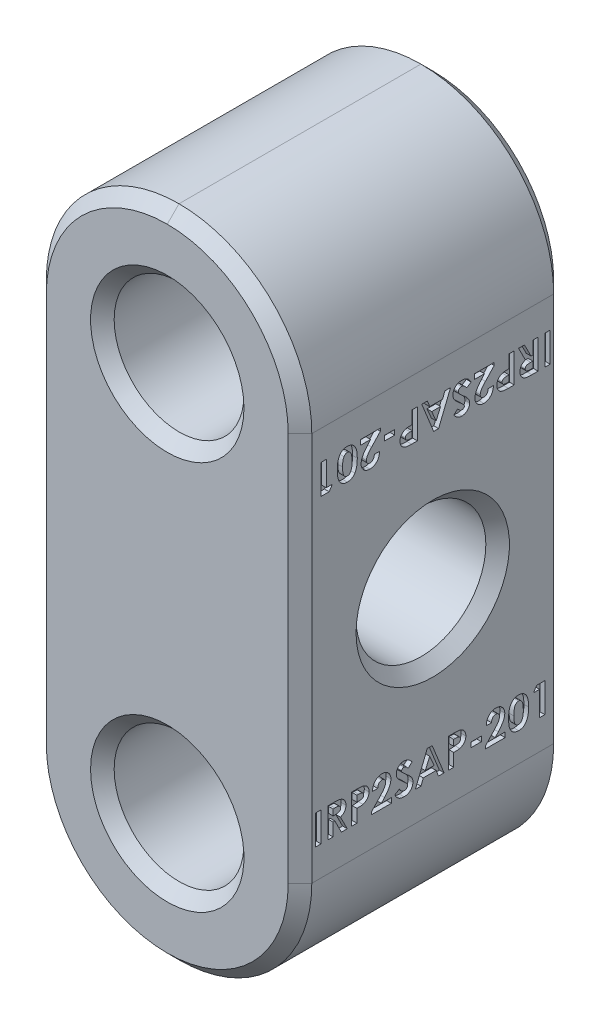
SolidWorks part; units mm, degrees
material "6061-T6 (SS)"
ref_plane "Front" through (0, 0, 0) normal (0, 0, 1) x (1, 0, 0)
ref_plane "Top" through (0, 0, 0) normal (0, 1, 0) x (1, 0, 0)
ref_plane "Right" through (0, 0, 0) normal (1, 0, 0) x (0, 0, -1)
sketch "Sketch1" plane through (0, 0, 0) normal (0, 0, 1) x (1, 0, 0)
  line L0 (0, 20.955) -> (0, 0) construction
  line L1 (-14.2875, -35.2425) -> (14.2875, -35.2425)
  line L2 (-14.2875, -35.2425) -> (-14.2875, 35.2425)
  line L3 (-14.2875, 35.2425) -> (14.2875, 35.2425)
  line L4 (14.2875, -35.2425) -> (14.2875, 35.2425)
  line L5 (-14.2875, -35.2425) -> (14.2875, 35.2425) construction
  line L6 (-14.2875, 35.2425) -> (14.2875, -35.2425) construction
  line L7 (0, 0) -> (0, -20.955) construction
  circle A0 centre (0, 20.955) radius 6.985
  circle A1 centre (0, -20.955) radius 6.985
  point P0 (0, 0)
  dimension "D4" = 13.97
  dimension "D1" = 28.575
  dimension "D2" = 70.485
  dimension "D3" = 14.2875
extrude "Boss-Extrude1" add sketch "Sketch1" along normal blind 28.575
sketch "Sketch2" plane through (14.2875, 0, 0) normal (1, 0, 0) x (0, 0, -1)
  line L0 (-28.575, 0) -> (-14.2875, 0) construction
  line L1 (-28.575, -35.2425) -> (-28.575, 35.2425) construction
  line L2 (-14.2875, 0) -> (0, 0) construction
  line L3 (0, -35.2425) -> (0, 35.2425) construction
  circle A0 centre (-14.2875, 0) radius 6.985
  dimension "D1" = 13.97
extrude "Cut-Extrude1" cut sketch "Sketch2" against normal through all
fillet "Fillet1" radius 14.2875 4 edges at (-14.2875, -35.2425, 14.2875) (-14.2875, 35.2425, 14.2875) (14.2875, 35.2425, 14.2875) (14.2875, -35.2425, 14.2875)
chamfer "Chamfer1" distance 1.27 angle 45 18 edges at (6.985, -20.955, 0) (6.985, -20.955, 28.575) (14.2875, 0, 7.3025) (-14.2875, 0, 7.3025) (6.985, 20.955, 0) (6.985, 20.955, 28.575) (-14.2875, 0, 0) (-10.1028, -31.0578, 0) (-10.1028, 31.0578, 0) (10.1028, -31.0578, 0) (10.1028, 31.0578, 0) (14.2875, 0, 0) (-14.2875, 0, 28.575) (-10.1028, -31.0578, 28.575) (-10.1028, 31.0578, 28.575) (10.1028, -31.0578, 28.575) (10.1028, 31.0578, 28.575) (14.2875, 0, 28.575)
sketch "Sketch3" plane through (14.2875, 0, 0) normal (1, 0, 0) x (0, 0, -1)
  line L0 (-28.575, -17.78) -> (0, -17.78) construction
  line L3 (-27.305, -20.955) -> (-1.27, -20.955) construction
  line L4 (-28.575, -20.955) -> (-28.575, 20.955) construction
  line L5 (0, 20.955) -> (0, -20.955) construction
  line L6 (-27.305, 17.78) -> (-1.27, 17.78) construction
  line L7 (-27.305, 20.955) -> (-27.305, -20.955) construction
  line L8 (-1.27, -20.955) -> (-1.27, 20.955) construction
  line L9 (-1.27, 20.955) -> (-27.305, 20.955) construction
  text T0 "<b>IRP2SAP-201</b>"
  text T1 "<b>IRP2SAP-201</b>"
  dimension "D1" = 3.175
  dimension "D2" = 3.175
extrude "Cut-Extrude2" cut sketch "Sketch3" against normal blind 0.508
sketch "Sketch4" plane through (-14.2875, 0, 0) normal (-1, 0, 0) x (0, 0, 1)
  line L0 (0, -17.78) -> (28.575, -17.78) construction
  line L1 (28.575, 20.955) -> (28.575, -20.955) construction
  line L2 (0, -20.955) -> (0, 20.955) construction
  line L3 (1.27, -20.955) -> (27.305, -20.955) construction
  line L4 (1.27, 17.78) -> (27.305, 17.78) construction
  line L5 (1.27, 20.955) -> (1.27, -20.955) construction
  line L6 (27.305, -20.955) -> (27.305, 20.955) construction
  line L7 (27.305, 20.955) -> (1.27, 20.955) construction
  text T0 "<b>IRP2SAP-201</b>"
  text T1 "<b>IRP2SAP-201</b>"
  dimension "D1" = 3.175
  dimension "D2" = 3.175
extrude "Cut-Extrude3" cut sketch "Sketch4" against normal blind 0.508
